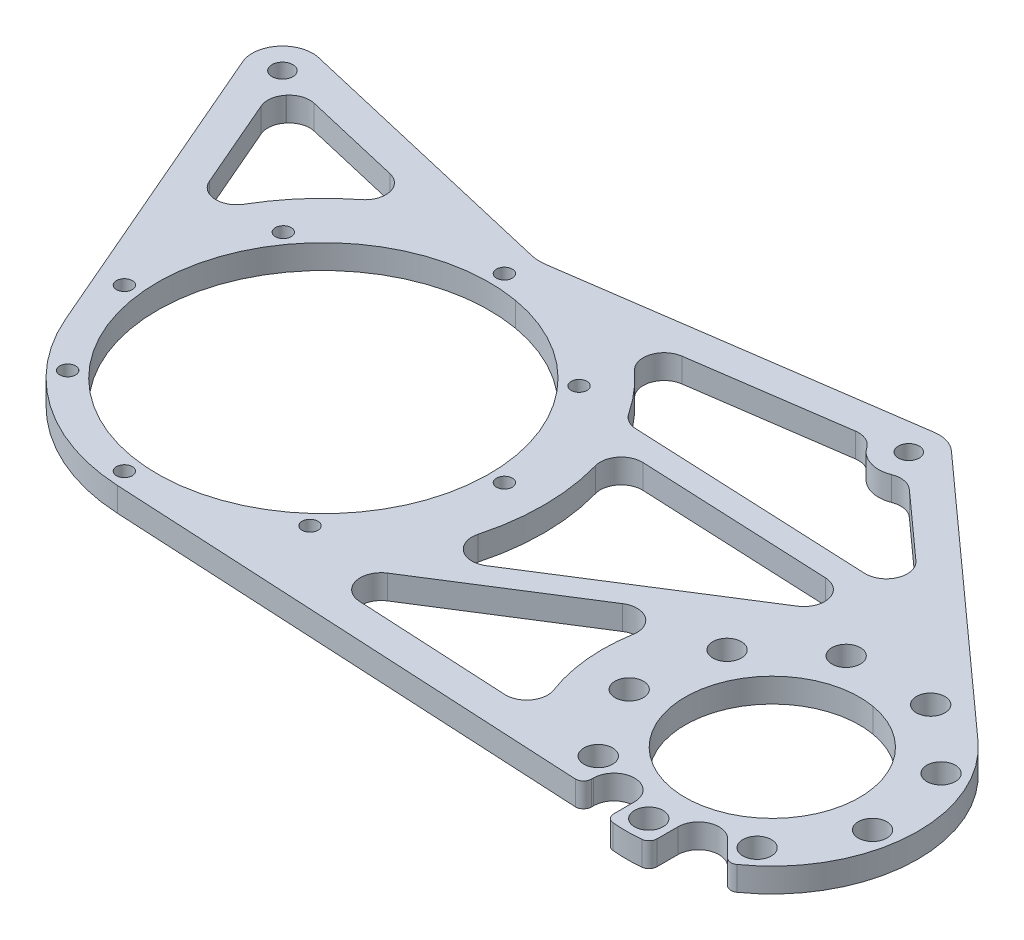
SolidWorks part; units mm, degrees
material "6061-T6 (SS)"
ref_plane "X-Y Datum" through (0, 0, 0) normal (0, 0, 1) x (1, 0, 0)
ref_plane "X-Z Datum" through (0, 0, 0) normal (0, 1, 0) x (1, 0, 0)
ref_plane "Y-Z Datum" through (0, 0, 0) normal (1, 0, 0) x (0, 0, -1)
sketch "Sketch2" plane through (0, 31.3819, 0) normal (0, 1, 0) x (1, 0, 0)
  line L0 (-693.7583, -176.702) -> (-693.7583, -183.2747) construction
  line L1 (-680.0808, -183.2747) -> (-680.0808, -176.702) construction
  line L2 (-668.9846, -172.1058) -> (-663.7197, -177.3707) construction
  line L3 (-693.7583, -176.702) -> (-693.7583, -183.2747)
  line L4 (-680.0808, -183.2747) -> (-680.0808, -176.702)
  line L5 (-668.9846, -172.1058) -> (-663.7197, -177.3707)
  line L6 (-966.641, -0.354) -> (-738.041, -0.354)
  line L7 (-727.7656, -5.5904) -> (-649.7224, -113.0358)
  line L9 (-977.8288, -19.0644) -> (-913.2312, -139.3061)
  line L10 (-706.7583, -177.279) -> (-706.7583, -176.702) construction
  line L11 (-706.7583, -177.279) -> (-706.7583, -176.702)
  line L12 (-861.9259, -171.8334) -> (-709.2983, -179.819)
  line L13 (-858.691, -110.0055) -> (-686.9195, -140.054) construction
  line L14 (-972.26, -24.9963) -> (-955.4664, -39.59) construction
  line L15 (-941.4162, -26.937) -> (-954.1775, -8.712) construction
  line L16 (-751.1929, -14.159) -> (-755.4346, -35.9995) construction
  line L17 (-737.4517, -41.8408) -> (-728.049, -21.6768) construction
  line L18 (-972.26, -24.9963) -> (-955.4664, -39.59)
  line L19 (-941.4162, -26.937) -> (-954.1775, -8.712)
  line L20 (-751.1929, -14.159) -> (-755.4346, -35.9995)
  line L21 (-737.4517, -41.8408) -> (-728.049, -21.6768)
  line L22 (-949.2186, -22.8753) -> (-746.0843, -28.2904)
  line L23 (-739.7146, -30.7335) -> (-656.1751, -105.8723)
  line L24 (-957.9647, -36.1729) -> (-915.5404, -134.527)
  arc A0 (-710.607, -179.4559) -> (-706.7583, -177.279) centre (-709.2983, -177.279) ccw construction
  arc A1 (-693.7583, -176.702) -> (-706.7583, -176.702) centre (-700.2583, -176.702) ccw construction
  arc A2 (-693.7583, -183.2747) -> (-691.4697, -185.8023) centre (-691.2183, -183.2747) ccw construction
  arc A3 (-691.4697, -185.8023) -> (-682.3694, -185.8023) centre (-686.9195, -140.054) ccw construction
  arc A4 (-682.3694, -185.8023) -> (-680.0808, -183.2747) centre (-682.6208, -183.2747) ccw construction
  arc A5 (-668.9846, -172.1058) -> (-680.0808, -176.702) centre (-673.5808, -176.702) ccw construction
  arc A6 (-663.7197, -177.3707) -> (-660.4619, -177.6519) centre (-661.9236, -175.5746) ccw construction
  arc A7 (-660.4619, -177.6519) -> (-710.607, -179.4559) centre (-686.9195, -140.054) ccw construction
  circle A8 centre (-858.691, -110.0055) radius 52.3875 construction
  circle A9 centre (-858.691, -110.0055) radius 61.9125 construction
  circle A10 centre (-738.041, -13.054) radius 12.7 construction
  circle A11 centre (-966.641, -13.054) radius 12.7 construction
  arc A12 (-710.607, -179.4559) -> (-706.7583, -177.279) centre (-709.2983, -177.279) ccw
  arc A13 (-693.7583, -176.702) -> (-706.7583, -176.702) centre (-700.2583, -176.702) ccw
  arc A14 (-693.7583, -183.2747) -> (-691.4697, -185.8023) centre (-691.2183, -183.2747) ccw
  arc A15 (-691.4697, -185.8023) -> (-682.3694, -185.8023) centre (-686.9195, -140.054) ccw
  arc A16 (-682.3694, -185.8023) -> (-680.0808, -183.2747) centre (-682.6208, -183.2747) ccw
  arc A17 (-668.9846, -172.1058) -> (-680.0808, -176.702) centre (-673.5808, -176.702) ccw
  arc A18 (-663.7197, -177.3707) -> (-660.4619, -177.6519) centre (-661.9236, -175.5746) ccw
  arc A19 (-660.4619, -177.6519) -> (-710.607, -179.4559) centre (-686.9195, -140.054) ccw
  circle A20 centre (-858.691, -110.0055) radius 52.3875
  circle A21 centre (-858.691, -110.0055) radius 61.9125
  circle A22 centre (-738.041, -13.054) radius 12.7
  circle A23 centre (-966.641, -13.054) radius 12.7
  circle A24 centre (-901.1618, -148.2463) radius 2.5 construction
  circle A25 centre (-915.528, -115.9793) radius 2.5 construction
  circle A26 centre (-904.9264, -76.4135) radius 2.5 construction
  circle A27 centre (-858.691, -52.8555) radius 2.5 construction
  circle A28 centre (-816.2203, -71.7646) radius 2.5 construction
  circle A29 centre (-801.541, -110.0055) radius 2.5 construction
  circle A30 centre (-820.4502, -152.4762) radius 2.5 construction
  circle A31 centre (-864.6648, -166.8424) radius 2.5 construction
  circle A32 centre (-901.1618, -148.2463) radius 2.5
  circle A33 centre (-915.528, -115.9793) radius 2.5
  circle A34 centre (-904.9264, -76.4135) radius 2.5
  circle A35 centre (-858.691, -52.8555) radius 2.5
  circle A36 centre (-816.2203, -71.7646) radius 2.5
  circle A37 centre (-801.541, -110.0055) radius 2.5
  circle A38 centre (-820.4502, -152.4762) radius 2.5
  circle A39 centre (-864.6648, -166.8424) radius 2.5
  circle A40 centre (-686.9195, -140.054) radius 27.4955 construction
  circle A41 centre (-686.9195, -140.054) radius 27.4955
  circle A42 centre (-711.9883, -169.9297) radius 4.5 construction
  circle A43 centre (-725.3271, -146.8263) radius 4.5 construction
  circle A44 centre (-720.6945, -120.554) radius 4.5 construction
  circle A45 centre (-700.2583, -103.406) radius 4.5 construction
  circle A46 centre (-673.5808, -103.406) radius 4.5 construction
  circle A47 centre (-653.1446, -120.554) radius 4.5 construction
  circle A48 centre (-648.512, -146.8263) radius 4.5 construction
  circle A49 centre (-661.8508, -169.9297) radius 4.5 construction
  circle A50 centre (-686.9195, -179.054) radius 4.5 construction
  circle A51 centre (-711.9883, -169.9297) radius 4.5
  circle A52 centre (-725.3271, -146.8263) radius 4.5
  circle A53 centre (-720.6945, -120.554) radius 4.5
  circle A54 centre (-700.2583, -103.406) radius 4.5
  circle A55 centre (-673.5808, -103.406) radius 4.5
  circle A56 centre (-653.1446, -120.554) radius 4.5
  circle A57 centre (-648.512, -146.8263) radius 4.5
  circle A58 centre (-661.8508, -169.9297) radius 4.5
  circle A59 centre (-686.9195, -179.054) radius 4.5
  circle A60 centre (-966.641, -13.054) radius 3.3
  circle A61 centre (-738.041, -13.054) radius 3.3
  arc A62 (-955.4664, -39.59) -> (-941.4162, -26.937) centre (-949.2186, -32.4003) ccw construction
  arc A63 (-749.3237, -37.1863) -> (-742.8448, -38.4445) centre (-746.0843, -37.8154) ccw construction
  arc A64 (-742.8448, -38.4445) -> (-749.3237, -37.1863) centre (-746.0843, -37.8154) ccw construction
  arc A65 (-755.4346, -35.9995) -> (-737.4517, -41.8408) centre (-746.0843, -37.8154) ccw construction
  arc A66 (-955.4664, -39.59) -> (-941.4162, -26.937) centre (-949.2186, -32.4003) ccw
  arc A67 (-749.3237, -37.1863) -> (-742.8448, -38.4445) centre (-746.0843, -37.8154) ccw
  arc A68 (-742.8448, -38.4445) -> (-749.3237, -37.1863) centre (-746.0843, -37.8154) ccw
  arc A69 (-755.4346, -35.9995) -> (-737.4517, -41.8408) centre (-746.0843, -37.8154) ccw
  circle A70 centre (-949.2186, -32.4003) radius 3.3
  circle A71 centre (-949.2186, -32.4003) radius 9.525
  circle A72 centre (-746.0843, -37.8154) radius 9.525
  point P94 (-949.2186, -32.4003)
  dimension "D1" = 6.6
  dimension "D2" = 6.6
  dimension "D3" = 6.6
extrude "Boss-Extrude1" add sketch "Sketch2" along normal blind 7.62 contours A21 A39 A38 A37 A36 A35 A34 A33 A32 A20 | A18 A19 A12 L11 A13 L3 A14 A15 A16 L4 A17 L5 A59 A58 A57 A56 A55 A54 A53 A52 A51 A41 | L13 A21 L12 A12 A19 | A21 L13 A19 L23 L21 A69 L20 L22 L19 A66 L18 L24 | A69 A72 A68 A67 | A72 L22 L20 | A72 L21 L23 | A71 L24 L18 | A71 L19 L22 | A71 A66 L22 A70 region at (-700.2583, 31.3819, 168.9016) region at (-773.051, 31.3819, 154.3682) region at (-890.9045, 31.3819, 160.8157) region at (-806.8861, 31.3819, 67.2042) region at (-956.9478, 31.3819, 38.0512) region at (-736.2382, 31.3819, 35.8095) region at (-956.6903, 31.3819, 37.8629) region at (-748.9437, 31.3819, 46.6182) region at (-752.4763, 31.3819, 29.8585) region at (-944.5842, 31.3819, 23.8004)
sketch "Sketch3" plane through (0, 31.3819, 0) normal (0, -1, 0) x (1, 0, 0)
  line L1 (-949.2186, 22.8753) -> (-746.0843, 28.2904) construction
  line L5 (-861.9259, 171.8334) -> (-709.2983, 179.819) construction
  line L6 (-977.8288, 19.0644) -> (-913.2312, 139.3061) construction
  line L7 (-727.7656, 5.5904) -> (-649.7224, 113.0358) construction
  line L13 (-751.1929, 14.159) -> (-755.4346, 35.9995) construction
  line L16 (-966.641, 0.354) -> (-738.041, 0.354) construction
  line L19 (-663.7197, 177.3707) -> (-668.9846, 172.1058)
  line L20 (-680.0808, 176.702) -> (-680.0808, 183.2747)
  line L21 (-693.7583, 183.2747) -> (-693.7583, 176.702)
  line L22 (-706.7583, 176.702) -> (-706.7583, 177.279)
  line L23 (-663.7197, 177.3707) -> (-668.9846, 172.1058)
  line L24 (-680.0808, 176.702) -> (-680.0808, 183.2747)
  line L25 (-693.7583, 183.2747) -> (-693.7583, 176.702)
  line L26 (-706.7583, 176.702) -> (-706.7583, 177.279)
  line L28 (-861.9259, 171.8334) -> (-709.2983, 179.819)
  line L29 (-977.8288, 19.0644) -> (-913.2312, 139.3061)
  line L30 (-727.7656, 5.5904) -> (-649.7224, 113.0358)
  line L31 (-966.641, 0.354) -> (-738.041, 0.354)
  line L34 (-737.4517, 41.8408) -> (-728.049, 21.6768) construction
  line L35 (-972.26, 24.9963) -> (-955.4664, 39.59) construction
  line L36 (-947.0539, 23.1246) -> (-856.9722, 44.1471)
  line L37 (-856.9722, 44.1471) -> (-747.4408, 28.3875)
  line L44 (-941.4162, 26.937) -> (-954.1775, 8.712) construction
  line L45 (-957.9647, 36.1729) -> (-915.5404, 134.527) construction
  line L46 (-739.7146, 30.7335) -> (-656.1751, 105.8723) construction
  line L47 (-861.9259, 171.8334) -> (-709.2983, 179.819)
  line L48 (-977.8288, 19.0644) -> (-913.2312, 139.3061)
  line L49 (-727.7656, 5.5904) -> (-649.7224, 113.0358)
  line L50 (-966.641, 0.354) -> (-738.041, 0.354)
  line L51 (-949.2186, 22.8753) -> (-746.0843, 28.2904)
  line L52 (-751.1929, 14.159) -> (-755.4346, 35.9995)
  line L53 (-737.4517, 41.8408) -> (-728.049, 21.6768)
  line L54 (-972.26, 24.9963) -> (-955.4664, 39.59)
  line L55 (-941.4162, 26.937) -> (-954.1775, 8.712)
  line L56 (-957.9647, 36.1729) -> (-915.5404, 134.527)
  line L57 (-739.7146, 30.7335) -> (-656.1751, 105.8723)
  arc A1 (-737.4517, 41.8408) -> (-755.4346, 35.9995) centre (-746.0843, 37.8154) ccw construction
  circle A3 centre (-966.641, 13.054) radius 12.7
  circle A5 centre (-966.641, 13.054) radius 12.7
  circle A7 centre (-738.041, 13.054) radius 12.7
  circle A9 centre (-738.041, 13.054) radius 12.7
  circle A11 centre (-858.691, 110.0055) radius 61.9125
  circle A13 centre (-858.691, 110.0055) radius 61.9125
  circle A15 centre (-858.691, 110.0055) radius 52.3875
  circle A17 centre (-858.691, 110.0055) radius 52.3875
  circle A19 centre (-686.9195, 140.054) radius 27.4955
  circle A21 centre (-686.9195, 140.054) radius 27.4955
  circle A23 centre (-864.6648, 166.8424) radius 2.5
  circle A25 centre (-864.6648, 166.8424) radius 2.5
  circle A27 centre (-820.4502, 152.4762) radius 2.5
  circle A29 centre (-820.4502, 152.4762) radius 2.5
  circle A31 centre (-801.541, 110.0055) radius 2.5
  circle A33 centre (-801.541, 110.0055) radius 2.5
  circle A35 centre (-816.2203, 71.7646) radius 2.5
  circle A37 centre (-816.2203, 71.7646) radius 2.5
  circle A39 centre (-858.691, 52.8555) radius 2.5
  circle A41 centre (-858.691, 52.8555) radius 2.5
  circle A43 centre (-904.9264, 76.4135) radius 2.5
  circle A46 centre (-904.9264, 76.4135) radius 2.5
  circle A47 centre (-915.528, 115.9793) radius 2.5
  circle A48 centre (-915.528, 115.9793) radius 2.5
  circle A49 centre (-901.1618, 148.2463) radius 2.5
  circle A50 centre (-901.1618, 148.2463) radius 2.5
  circle A51 centre (-720.6945, 120.554) radius 4.5
  circle A52 centre (-720.6945, 120.554) radius 4.5
  circle A68 centre (-725.3271, 146.8263) radius 4.5
  circle A69 centre (-725.3271, 146.8263) radius 4.5
  circle A70 centre (-711.9883, 169.9297) radius 4.5
  circle A71 centre (-711.9883, 169.9297) radius 4.5
  circle A72 centre (-738.041, 13.054) radius 3.3
  circle A73 centre (-738.041, 13.054) radius 3.3
  circle A74 centre (-966.641, 13.054) radius 3.3
  circle A75 centre (-966.641, 13.054) radius 3.3
  circle A76 centre (-686.9195, 179.054) radius 4.5
  circle A77 centre (-686.9195, 179.054) radius 4.5
  circle A78 centre (-661.8508, 169.9297) radius 4.5
  circle A79 centre (-661.8508, 169.9297) radius 4.5
  circle A80 centre (-648.512, 146.8263) radius 4.5
  circle A81 centre (-648.512, 146.8263) radius 4.5
  circle A82 centre (-653.1446, 120.554) radius 4.5
  circle A83 centre (-653.1446, 120.554) radius 4.5
  circle A84 centre (-673.5808, 103.406) radius 4.5
  circle A85 centre (-673.5808, 103.406) radius 4.5
  circle A86 centre (-700.2583, 103.406) radius 4.5
  circle A87 centre (-700.2583, 103.406) radius 4.5
  arc A95 (-710.607, 179.4559) -> (-660.4619, 177.6519) centre (-686.9195, 140.054) ccw
  arc A96 (-660.4619, 177.6519) -> (-663.7197, 177.3707) centre (-661.9236, 175.5746) ccw
  arc A97 (-680.0808, 176.702) -> (-668.9846, 172.1058) centre (-673.5808, 176.702) ccw
  arc A98 (-680.0808, 183.2747) -> (-682.3694, 185.8023) centre (-682.6208, 183.2747) ccw
  arc A99 (-682.3694, 185.8023) -> (-691.4697, 185.8023) centre (-686.9195, 140.054) ccw
  arc A100 (-691.4697, 185.8023) -> (-693.7583, 183.2747) centre (-691.2183, 183.2747) ccw
  arc A101 (-706.7583, 176.702) -> (-693.7583, 176.702) centre (-700.2583, 176.702) ccw
  arc A102 (-706.7583, 177.279) -> (-710.607, 179.4559) centre (-709.2983, 177.279) ccw
  arc A103 (-710.607, 179.4559) -> (-660.4619, 177.6519) centre (-686.9195, 140.054) ccw
  arc A104 (-660.4619, 177.6519) -> (-663.7197, 177.3707) centre (-661.9236, 175.5746) ccw
  arc A105 (-680.0808, 176.702) -> (-668.9846, 172.1058) centre (-673.5808, 176.702) ccw
  arc A106 (-680.0808, 183.2747) -> (-682.3694, 185.8023) centre (-682.6208, 183.2747) ccw
  arc A107 (-682.3694, 185.8023) -> (-691.4697, 185.8023) centre (-686.9195, 140.054) ccw
  arc A108 (-691.4697, 185.8023) -> (-693.7583, 183.2747) centre (-691.2183, 183.2747) ccw
  arc A109 (-706.7583, 176.702) -> (-693.7583, 176.702) centre (-700.2583, 176.702) ccw
  arc A110 (-706.7583, 177.279) -> (-710.607, 179.4559) centre (-709.2983, 177.279) ccw
  circle A152 centre (-746.0843, 37.8154) radius 9.525
  circle A153 centre (-746.0843, 37.8154) radius 9.525
  circle A154 centre (-949.2186, 32.4003) radius 9.525
  circle A155 centre (-949.2186, 32.4003) radius 9.525
  circle A156 centre (-949.2186, 32.4003) radius 3.3
  circle A157 centre (-949.2186, 32.4003) radius 3.3
  arc A158 (-941.4162, 26.937) -> (-955.4664, 39.59) centre (-949.2186, 32.4003) ccw construction
  arc A159 (-742.8448, 38.4445) -> (-749.3237, 37.1863) centre (-746.0843, 37.8154) ccw
  arc A160 (-749.3237, 37.1863) -> (-742.8448, 38.4445) centre (-746.0843, 37.8154) ccw
  arc A161 (-742.8448, 38.4445) -> (-749.3237, 37.1863) centre (-746.0843, 37.8154) ccw
  arc A162 (-749.3237, 37.1863) -> (-742.8448, 38.4445) centre (-746.0843, 37.8154) ccw
  arc A163 (-737.4517, 41.8408) -> (-755.4346, 35.9995) centre (-746.0843, 37.8154) ccw
  arc A164 (-941.4162, 26.937) -> (-955.4664, 39.59) centre (-949.2186, 32.4003) ccw
  dimension "D24" = 0
  dimension "D25" = 0
  dimension "D26" = 90.0818
  dimension "D27" = 21.0225
  dimension "D1" = 0
  dimension "D2" = 0
  dimension "D3" = 0
  dimension "D4" = 0
  dimension "D5" = 0
  dimension "D6" = 0
  dimension "D7" = 0
  dimension "D8" = 0
  dimension "D9" = 0
  dimension "D10" = 0
  dimension "D11" = 0
  dimension "D12" = 0
  dimension "D13" = 0
  dimension "D14" = 0
  dimension "D15" = 0
  dimension "D16" = 0
  dimension "D17" = 0
  dimension "D18" = 0
  dimension "D19" = 0
  dimension "D20" = 0
  dimension "D21" = 0
  dimension "D22" = 0
  dimension "D23" = 0
  dimension "D52" = 0
  dimension "D53" = 0
  dimension "D54" = 0
  dimension "D55" = 0
ref_point "Point1"
ref_point "Point2"
ref_plane "Plane1" through (-858.691, 31.3819, 110.0055) normal (0.985, 0, 0.1723) x (0.1723, 0, -0.985)
ref_plane "Plane2" through (-686.9195, 31.3819, 140.054) normal (-0.985, 0, -0.1723) x (-0.1723, 0, 0.985)
split line "Split Line1"
split line "Split Line2"
ref_axis "Axis1" through (-858.691, 39.0019, 110.0055) along (0, -1, 0)
ref_axis "Axis2" through (-686.9195, 39.0019, 140.054) along (0, -1, 0)
extrude "Cut-Extrude1" cut sketch "Sketch3" against normal through all contours L36 L55 L51 L52 L37 | A155 L51 L55 L36 | A153 L37 L52 L51 region at (-751.5495, 31.3819, 28.5688) region at (-850.6911, 31.3819, 31.7926) region at (-945.2616, 31.3819, 23.2848)
fillet "Fillet2" radius 12.7 1 edges at (-856.9722, 35.1919, 44.1471)
sketch "Sketch4" plane through (0, 31.3819, 0) normal (0, -1, 0) x (1, 0, 0)
  line L0 (-861.9259, 171.8334) -> (-709.2983, 179.819) construction
  line L1 (-727.7656, 5.5904) -> (-649.7224, 113.0358) construction
  line L2 (-977.8288, 19.0644) -> (-913.2312, 139.3061) construction
  line L4 (-706.7583, 176.702) -> (-706.7583, 177.279)
  line L5 (-663.7197, 177.3707) -> (-668.9846, 172.1058)
  line L6 (-680.0808, 176.702) -> (-680.0808, 183.2747)
  line L7 (-693.7583, 183.2747) -> (-693.7583, 176.702)
  line L8 (-706.7583, 176.702) -> (-706.7583, 177.279)
  line L9 (-663.7197, 177.3707) -> (-668.9846, 172.1058)
  line L10 (-680.0808, 176.702) -> (-680.0808, 183.2747)
  line L11 (-693.7583, 183.2747) -> (-693.7583, 176.702)
  line L13 (-966.641, 0.354) -> (-738.041, 0.354) construction
  line L14 (-861.9259, 171.8334) -> (-709.2983, 179.819)
  line L15 (-727.7656, 5.5904) -> (-649.7224, 113.0358)
  line L16 (-977.8288, 19.0644) -> (-913.2312, 139.3061)
  line L17 (-861.9259, 171.8334) -> (-709.2983, 179.819) construction
  line L19 (-966.641, 0.354) -> (-738.041, 0.354)
  line L20 (-924.6037, 87.863) -> (-948.1369, 33.3048)
  line L21 (-948.1369, 33.3048) -> (-888.5504, 47.2106)
  line L22 (-732.3805, 168.4374) -> (-812.7818, 164.2308)
  line L23 (-812.7818, 164.2308) -> (-733.9678, 114.3873)
  line L24 (-799.833, 147.0258) -> (-703.8013, 86.2934)
  line L25 (-703.8013, 86.2934) -> (-794.9695, 82.1785)
  line L26 (-824.108, 49.6832) -> (-755.4008, 39.7974)
  line L27 (-798.9847, 74.3695) -> (-701.5009, 78.7695)
  line L28 (-701.5009, 78.7695) -> (-739.4428, 44.643)
  line L29 (-977.8288, 19.0644) -> (-913.2312, 139.3061) construction
  line L30 (-727.7656, 5.5904) -> (-649.7224, 113.0358) construction
  line L31 (-966.641, 0.354) -> (-738.041, 0.354) construction
  line L32 (-663.7197, 177.3707) -> (-668.9846, 172.1058)
  line L33 (-680.0808, 176.702) -> (-680.0808, 183.2747)
  line L34 (-693.7583, 183.2747) -> (-693.7583, 176.702)
  line L35 (-706.7583, 176.702) -> (-706.7583, 177.279)
  line L36 (-663.7197, 177.3707) -> (-668.9846, 172.1058)
  line L37 (-680.0808, 176.702) -> (-680.0808, 183.2747)
  line L38 (-693.7583, 183.2747) -> (-693.7583, 176.702)
  line L39 (-706.7583, 176.702) -> (-706.7583, 177.279)
  line L40 (-949.2186, 22.8753) -> (-746.0843, 28.2904) construction
  line L41 (-751.1929, 14.159) -> (-755.4346, 35.9995) construction
  line L42 (-737.4517, 41.8408) -> (-728.049, 21.6768) construction
  line L43 (-972.26, 24.9963) -> (-955.4664, 39.59) construction
  line L44 (-941.4162, 26.937) -> (-954.1775, 8.712) construction
  line L45 (-957.9647, 36.1729) -> (-915.5404, 134.527) construction
  line L46 (-739.7146, 30.7335) -> (-656.1751, 105.8723) construction
  line L47 (-861.9259, 171.8334) -> (-709.2983, 179.819)
  line L48 (-977.8288, 19.0644) -> (-913.2312, 139.3061)
  line L49 (-727.7656, 5.5904) -> (-649.7224, 113.0358)
  line L50 (-966.641, 0.354) -> (-738.041, 0.354)
  line L51 (-949.2186, 22.8753) -> (-746.0843, 28.2904)
  line L52 (-751.1929, 14.159) -> (-755.4346, 35.9995)
  line L53 (-737.4517, 41.8408) -> (-728.049, 21.6768)
  line L54 (-972.26, 24.9963) -> (-955.4664, 39.59)
  line L55 (-941.4162, 26.937) -> (-954.1775, 8.712)
  line L56 (-957.9647, 36.1729) -> (-915.5404, 134.527)
  line L57 (-739.7146, 30.7335) -> (-656.1751, 105.8723)
  line L58 (-947.0539, 23.1246) -> (-859.3005, 43.6037) construction
  line L60 (-854.6056, 43.8066) -> (-747.4408, 28.3875) construction
  circle A1 centre (-858.691, 110.0055) radius 52.3875
  circle A2 centre (-858.691, 110.0055) radius 52.3875
  circle A3 centre (-858.691, 110.0055) radius 61.9125
  circle A4 centre (-858.691, 110.0055) radius 61.9125
  circle A5 centre (-738.041, 13.054) radius 12.7
  circle A6 centre (-738.041, 13.054) radius 12.7
  circle A7 centre (-966.641, 13.054) radius 12.7
  circle A8 centre (-966.641, 13.054) radius 12.7
  circle A9 centre (-858.691, 52.8555) radius 2.5
  circle A10 centre (-858.691, 52.8555) radius 2.5
  circle A11 centre (-816.2203, 71.7646) radius 2.5
  circle A12 centre (-816.2203, 71.7646) radius 2.5
  circle A13 centre (-801.541, 110.0055) radius 2.5
  circle A14 centre (-801.541, 110.0055) radius 2.5
  circle A15 centre (-820.4502, 152.4762) radius 2.5
  circle A16 centre (-820.4502, 152.4762) radius 2.5
  circle A17 centre (-864.6648, 166.8424) radius 2.5
  circle A18 centre (-864.6648, 166.8424) radius 2.5
  circle A19 centre (-686.9195, 140.054) radius 27.4955
  circle A20 centre (-686.9195, 140.054) radius 27.4955
  circle A21 centre (-725.3271, 146.8263) radius 4.5
  circle A22 centre (-725.3271, 146.8263) radius 4.5
  circle A23 centre (-720.6945, 120.554) radius 4.5
  circle A24 centre (-720.6945, 120.554) radius 4.5
  circle A25 centre (-901.1618, 148.2463) radius 2.5
  circle A26 centre (-901.1618, 148.2463) radius 2.5
  circle A27 centre (-915.528, 115.9793) radius 2.5
  circle A28 centre (-915.528, 115.9793) radius 2.5
  circle A29 centre (-904.9264, 76.4135) radius 2.5
  circle A30 centre (-904.9264, 76.4135) radius 2.5
  circle A31 centre (-661.8508, 169.9297) radius 4.5
  circle A32 centre (-661.8508, 169.9297) radius 4.5
  circle A33 centre (-686.9195, 179.054) radius 4.5
  circle A34 centre (-686.9195, 179.054) radius 4.5
  circle A35 centre (-966.641, 13.054) radius 3.3
  circle A36 centre (-966.641, 13.054) radius 3.3
  circle A37 centre (-738.041, 13.054) radius 3.3
  circle A38 centre (-738.041, 13.054) radius 3.3
  circle A39 centre (-711.9883, 169.9297) radius 4.5
  circle A40 centre (-711.9883, 169.9297) radius 4.5
  circle A41 centre (-700.2583, 103.406) radius 4.5
  circle A42 centre (-700.2583, 103.406) radius 4.5
  circle A43 centre (-673.5808, 103.406) radius 4.5
  circle A44 centre (-673.5808, 103.406) radius 4.5
  circle A45 centre (-653.1446, 120.554) radius 4.5
  circle A46 centre (-653.1446, 120.554) radius 4.5
  circle A47 centre (-648.512, 146.8263) radius 4.5
  circle A48 centre (-648.512, 146.8263) radius 4.5
  arc A49 (-888.5504, 47.2106) -> (-924.6037, 87.863) centre (-858.691, 110.0055) cw
  arc A50 (-732.3805, 168.4374) -> (-733.9678, 114.3873) centre (-686.9195, 140.054) ccw
  arc A51 (-799.833, 147.0258) -> (-794.9695, 82.1785) centre (-858.691, 110.0055) cw
  arc A52 (-824.108, 49.6832) -> (-798.9847, 74.3695) centre (-858.691, 110.0055) ccw
  arc A53 (-737.4517, 41.8408) -> (-755.4346, 35.9995) centre (-746.0843, 37.8154) ccw construction
  circle A54 centre (-966.641, 13.054) radius 12.7
  circle A55 centre (-966.641, 13.054) radius 12.7
  arc A56 (-706.7583, 177.279) -> (-710.607, 179.4559) centre (-709.2983, 177.279) ccw
  arc A57 (-710.607, 179.4559) -> (-660.4619, 177.6519) centre (-686.9195, 140.054) ccw
  arc A58 (-660.4619, 177.6519) -> (-663.7197, 177.3707) centre (-661.9236, 175.5746) ccw
  arc A59 (-680.0808, 176.702) -> (-668.9846, 172.1058) centre (-673.5808, 176.702) ccw
  arc A60 (-680.0808, 183.2747) -> (-682.3694, 185.8023) centre (-682.6208, 183.2747) ccw
  arc A61 (-682.3694, 185.8023) -> (-691.4697, 185.8023) centre (-686.9195, 140.054) ccw
  arc A62 (-691.4697, 185.8023) -> (-693.7583, 183.2747) centre (-691.2183, 183.2747) ccw
  arc A63 (-706.7583, 176.702) -> (-693.7583, 176.702) centre (-700.2583, 176.702) ccw
  arc A64 (-706.7583, 177.279) -> (-710.607, 179.4559) centre (-709.2983, 177.279) ccw
  arc A65 (-710.607, 179.4559) -> (-660.4619, 177.6519) centre (-686.9195, 140.054) ccw
  arc A66 (-660.4619, 177.6519) -> (-663.7197, 177.3707) centre (-661.9236, 175.5746) ccw
  arc A67 (-680.0808, 176.702) -> (-668.9846, 172.1058) centre (-673.5808, 176.702) ccw
  arc A68 (-680.0808, 183.2747) -> (-682.3694, 185.8023) centre (-682.6208, 183.2747) ccw
  arc A69 (-682.3694, 185.8023) -> (-691.4697, 185.8023) centre (-686.9195, 140.054) ccw
  arc A70 (-691.4697, 185.8023) -> (-693.7583, 183.2747) centre (-691.2183, 183.2747) ccw
  arc A71 (-706.7583, 176.702) -> (-693.7583, 176.702) centre (-700.2583, 176.702) ccw
  circle A72 centre (-738.041, 13.054) radius 12.7
  circle A73 centre (-738.041, 13.054) radius 12.7
  circle A74 centre (-858.691, 110.0055) radius 61.9125
  circle A75 centre (-858.691, 110.0055) radius 61.9125
  circle A76 centre (-858.691, 110.0055) radius 52.3875
  circle A77 centre (-858.691, 110.0055) radius 52.3875
  circle A78 centre (-686.9195, 140.054) radius 27.4955
  circle A79 centre (-686.9195, 140.054) radius 27.4955
  circle A80 centre (-864.6648, 166.8424) radius 2.5
  circle A81 centre (-864.6648, 166.8424) radius 2.5
  circle A82 centre (-820.4502, 152.4762) radius 2.5
  circle A83 centre (-820.4502, 152.4762) radius 2.5
  circle A84 centre (-801.541, 110.0055) radius 2.5
  circle A85 centre (-801.541, 110.0055) radius 2.5
  circle A86 centre (-816.2203, 71.7646) radius 2.5
  circle A87 centre (-816.2203, 71.7646) radius 2.5
  circle A88 centre (-858.691, 52.8555) radius 2.5
  circle A89 centre (-858.691, 52.8555) radius 2.5
  circle A90 centre (-904.9264, 76.4135) radius 2.5
  circle A91 centre (-904.9264, 76.4135) radius 2.5
  circle A92 centre (-915.528, 115.9793) radius 2.5
  circle A93 centre (-915.528, 115.9793) radius 2.5
  circle A94 centre (-901.1618, 148.2463) radius 2.5
  circle A95 centre (-901.1618, 148.2463) radius 2.5
  circle A96 centre (-720.6945, 120.554) radius 4.5
  circle A97 centre (-720.6945, 120.554) radius 4.5
  circle A98 centre (-725.3271, 146.8263) radius 4.5
  circle A99 centre (-725.3271, 146.8263) radius 4.5
  circle A100 centre (-711.9883, 169.9297) radius 4.5
  circle A101 centre (-711.9883, 169.9297) radius 4.5
  circle A102 centre (-738.041, 13.054) radius 3.3
  circle A103 centre (-738.041, 13.054) radius 3.3
  circle A104 centre (-966.641, 13.054) radius 3.3
  circle A105 centre (-966.641, 13.054) radius 3.3
  circle A106 centre (-686.9195, 179.054) radius 4.5
  circle A107 centre (-686.9195, 179.054) radius 4.5
  circle A108 centre (-661.8508, 169.9297) radius 4.5
  circle A109 centre (-661.8508, 169.9297) radius 4.5
  circle A110 centre (-648.512, 146.8263) radius 4.5
  circle A111 centre (-648.512, 146.8263) radius 4.5
  circle A112 centre (-653.1446, 120.554) radius 4.5
  circle A113 centre (-653.1446, 120.554) radius 4.5
  circle A114 centre (-673.5808, 103.406) radius 4.5
  circle A115 centre (-673.5808, 103.406) radius 4.5
  circle A116 centre (-700.2583, 103.406) radius 4.5
  circle A117 centre (-700.2583, 103.406) radius 4.5
  circle A118 centre (-746.0843, 37.8154) radius 9.525
  circle A119 centre (-746.0843, 37.8154) radius 9.525
  circle A120 centre (-949.2186, 32.4003) radius 9.525
  circle A121 centre (-949.2186, 32.4003) radius 9.525
  circle A122 centre (-949.2186, 32.4003) radius 3.3
  circle A123 centre (-949.2186, 32.4003) radius 3.3
  arc A124 (-941.4162, 26.937) -> (-955.4664, 39.59) centre (-949.2186, 32.4003) ccw construction
  arc A125 (-742.8448, 38.4445) -> (-749.3237, 37.1863) centre (-746.0843, 37.8154) ccw
  arc A126 (-749.3237, 37.1863) -> (-742.8448, 38.4445) centre (-746.0843, 37.8154) ccw
  arc A127 (-742.8448, 38.4445) -> (-749.3237, 37.1863) centre (-746.0843, 37.8154) ccw
  arc A128 (-749.3237, 37.1863) -> (-742.8448, 38.4445) centre (-746.0843, 37.8154) ccw
  arc A129 (-737.4517, 41.8408) -> (-755.4346, 35.9995) centre (-746.0843, 37.8154) ccw
  arc A130 (-941.4162, 26.937) -> (-955.4664, 39.59) centre (-949.2186, 32.4003) ccw
  arc A135 (-710.607, 179.4559) -> (-660.4619, 177.6519) centre (-686.9195, 140.054) ccw
  arc A136 (-660.4619, 177.6519) -> (-663.7197, 177.3707) centre (-661.9236, 175.5746) ccw
  arc A137 (-680.0808, 176.702) -> (-668.9846, 172.1058) centre (-673.5808, 176.702) ccw
  arc A138 (-680.0808, 183.2747) -> (-682.3694, 185.8023) centre (-682.6208, 183.2747) ccw
  arc A139 (-682.3694, 185.8023) -> (-691.4697, 185.8023) centre (-686.9195, 140.054) ccw
  arc A140 (-691.4697, 185.8023) -> (-693.7583, 183.2747) centre (-691.2183, 183.2747) ccw
  arc A141 (-706.7583, 176.702) -> (-693.7583, 176.702) centre (-700.2583, 176.702) ccw
  arc A142 (-706.7583, 177.279) -> (-710.607, 179.4559) centre (-709.2983, 177.279) ccw
  arc A143 (-710.607, 179.4559) -> (-660.4619, 177.6519) centre (-686.9195, 140.054) ccw
  arc A144 (-660.4619, 177.6519) -> (-663.7197, 177.3707) centre (-661.9236, 175.5746) ccw
  arc A145 (-680.0808, 176.702) -> (-668.9846, 172.1058) centre (-673.5808, 176.702) ccw
  arc A146 (-680.0808, 183.2747) -> (-682.3694, 185.8023) centre (-682.6208, 183.2747) ccw
  arc A147 (-682.3694, 185.8023) -> (-691.4697, 185.8023) centre (-686.9195, 140.054) ccw
  arc A148 (-691.4697, 185.8023) -> (-693.7583, 183.2747) centre (-691.2183, 183.2747) ccw
  arc A149 (-706.7583, 176.702) -> (-693.7583, 176.702) centre (-700.2583, 176.702) ccw
  arc A150 (-706.7583, 177.279) -> (-710.607, 179.4559) centre (-709.2983, 177.279) ccw
  point P74 (-937.9929, 49.7032)
  point P202 (-886.302, 46.1901)
  point P215 (-754.4736, 33.3048)
  point P225 (-711.9883, 44.9518)
  point P233 (0, 0)
  point P234 (-686.9195, 79.4383)
  point P240 (-703.8013, 78.6656)
  point P241 (-741.2662, 46.032)
  dimension "D26" = 7.62
  dimension "D29" = 7.62
  dimension "D30" = 7.62
  dimension "D35" = 0
  dimension "D39" = 7.62
  dimension "D27" = 0
  dimension "D28" = 0
  dimension "D31" = 10.16
  dimension "D32" = 7.62
  dimension "D33" = 93.2524
  dimension "D34" = 49.8435
  dimension "D36" = 91.1683
  dimension "D37" = 4.1149
  dimension "D38" = 10.16
  dimension "D40" = 7.62
  dimension "D67" = 10.16
  dimension "D68" = 10.16
  dimension "D69" = 10.16
  dimension "D1" = 0
  dimension "D2" = 0
  dimension "D3" = 0
  dimension "D4" = 0
  dimension "D5" = 0
  dimension "D6" = 0
  dimension "D7" = 0
  dimension "D8" = 0
  dimension "D9" = 0
  dimension "D10" = 0
  dimension "D11" = 0
  dimension "D12" = 0
  dimension "D13" = 0
  dimension "D14" = 0
  dimension "D15" = 0
  dimension "D16" = 0
  dimension "D17" = 0
  dimension "D18" = 0
  dimension "D19" = 0
  dimension "D20" = 0
  dimension "D21" = 0
  dimension "D22" = 0
  dimension "D23" = 0
  dimension "D24" = 0
  dimension "D25" = 0
  dimension "D41" = 0
  dimension "D42" = 0
  dimension "D43" = 0
  dimension "D44" = 0
  dimension "D45" = 0
  dimension "D46" = 0
  dimension "D47" = 0
  dimension "D48" = 0
  dimension "D49" = 0
  dimension "D50" = 0
  dimension "D51" = 0
  dimension "D52" = 0
  dimension "D53" = 0
  dimension "D54" = 0
  dimension "D55" = 0
  dimension "D56" = 0
  dimension "D57" = 0
  dimension "D58" = 0
  dimension "D59" = 0
  dimension "D60" = 0
  dimension "D61" = 0
  dimension "D62" = 0
  dimension "D63" = 0
  dimension "D64" = 0
  dimension "D65" = 0
  dimension "D66" = 0
extrude "Cut-Extrude2" cut sketch "Sketch4" against normal through all contours L21 A49 L20 A8 | A52 L26 A6 L28 L27 | L24 A51 L25 | A50 L22 L23 region at (-763.7407, 31.3819, 60.8107) region at (-921.8341, 31.3819, 54.9859) region at (-763.0306, 31.3819, 150.0769) region at (-762.4094, 31.3819, 103.8535)
fillet "Fillet3" radius 6.604 15 edges at (-733.9678, 35.1919, 114.3873) (-732.3805, 35.1919, 168.4374) (-812.7818, 35.1919, 164.2308) (-703.8013, 35.1919, 86.2934) (-794.9695, 35.1919, 82.1785) (-799.833, 35.1919, 147.0258) (-701.5009, 35.1919, 78.7695) (-798.9847, 35.1919, 74.3695) (-824.108, 35.1919, 49.6832) (-888.5504, 35.1919, 47.2106) (-924.6037, 35.1919, 87.863) (-739.4428, 35.1919, 44.643) (-755.4008, 35.1919, 39.7974) (-940.1078, 35.1919, 35.1786) (-944.8714, 35.1919, 40.8754)
split line "Split Line3"
sketch "Sketch2<4>" plane through (0, 31.3819, 0) normal (0, 1, 0) x (1, 0, 0) same geometry as "Sketch2"
